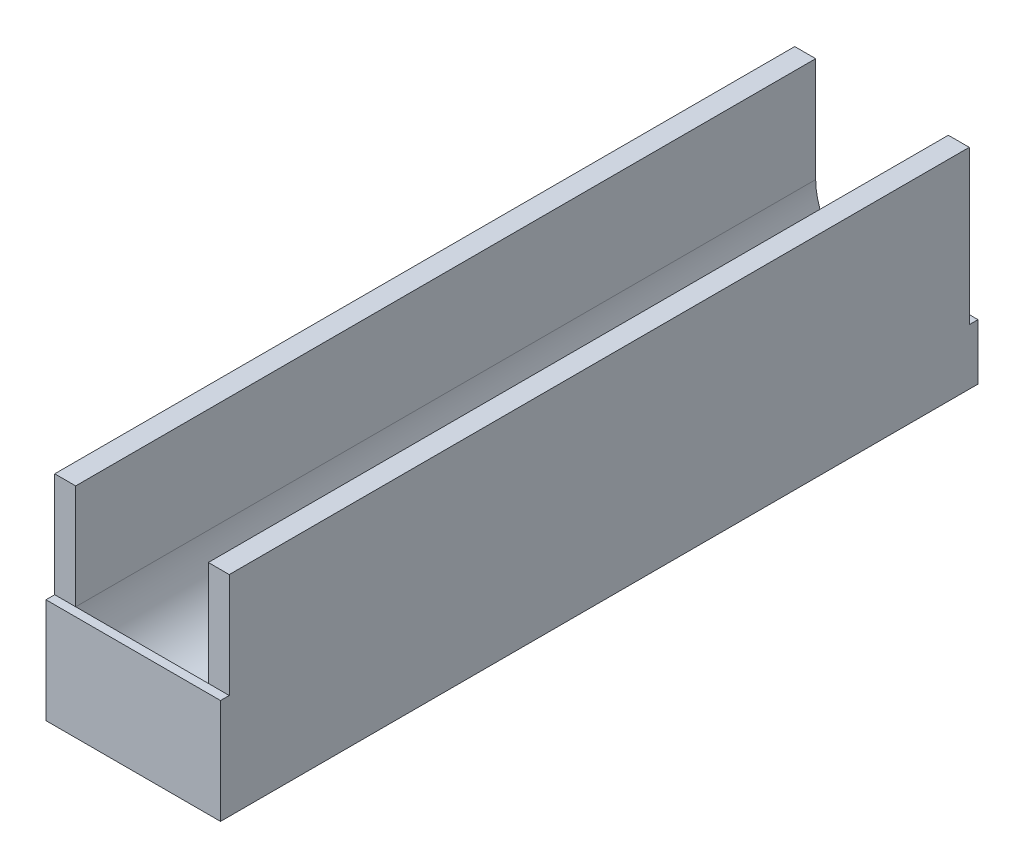
SolidWorks part; units mm, degrees
ref_plane "Front Plane" through (0, 0, 0) normal (0, 0, 1) x (1, 0, 0)
ref_plane "Top Plane" through (0, 0, 0) normal (0, 1, 0) x (1, 0, 0)
ref_plane "Right Plane" through (0, 0, 0) normal (1, 0, 0) x (0, 0, -1)
sketch "Sketch1" plane through (0, 0, 0) normal (0, 0, 1) x (1, 0, 0)
  line L1 (-15.875, 0) -> (15.875, 0)
  line L2 (-15.875, 0) -> (-15.875, 38.1)
  line L3 (-15.875, 38.1) -> (15.875, 38.1)
  line L4 (15.875, 0) -> (15.875, 38.1)
  dimension "D1" = 38.1
  dimension "D2" = 31.75
  dimension "D3" = 15.875
extrude "Boss-Extrude1" add sketch "Sketch1" along normal blind 134.62
sketch "Sketch2" plane through (0, 0, 134.62) normal (0, 0, 1) x (1, 0, 0)
  line L0 (-12.065, 19.05) -> (-12.065, 38.1)
  line L1 (15.875, 38.1) -> (-15.875, 38.1) construction
  line L2 (12.065, 19.05) -> (12.065, 38.1)
  line L3 (12.065, 38.1) -> (-12.065, 38.1)
  arc A2 (-12.065, 19.05) -> (12.065, 19.05) centre (0, 19.05) ccw
  dimension "D1" = 24.13
  dimension "D3" = 19.05
  dimension "D2" = 0
  dimension "D4" = 19.05
extrude "Cut-Extrude1" cut sketch "Sketch2" against normal through all
sketch "Sketch3" plane through (0, 0, 0) normal (0, -1, 0) x (1, 0, 0)
  line L0 (-15.875, 134.62) -> (15.875, 134.62) construction
  line L1 (-15.875, 0) -> (15.875, 0) construction
  circle A0 centre (-12.7, 128.27) radius 2
  circle A1 centre (12.7, 6.35) radius 2
  point P6 (0, 134.62)
  dimension "D1" = 4
  dimension "D2" = 4
  dimension "D6" = 6.35
  dimension "D3" = 12.7
  dimension "D4" = 12.7
  dimension "D5" = 6.35
extrude "Cut-Extrude2" cut sketch "Sketch3" against normal blind 7
sketch "Sketch4" plane through (0, 0, 134.62) normal (0, 0, 1) x (1, 0, 0)
  line L0 (-15.875, 38.1) -> (-15.875, 0) construction
  line L1 (15.875, 0) -> (-15.875, 0)
  line L2 (15.875, 0) -> (15.875, 19.05)
  line L3 (15.875, 19.05) -> (-15.875, 19.05)
  line L4 (-15.875, 0) -> (-15.875, 19.05)
  dimension "D1" = 19.05
extrude "Boss-Extrude2" add sketch "Sketch4" along normal blind 1.5875
sketch "Sketch5" plane through (0, 0, 0) normal (0, 0, -1) x (-1, 0, 0)
  line L0 (15.875, 38.1) -> (15.875, 0) construction
  line L1 (-15.875, 0) -> (15.875, 0)
  line L2 (-15.875, 0) -> (-15.875, 10.16)
  line L3 (-15.875, 10.16) -> (15.875, 10.16)
  line L4 (15.875, 0) -> (15.875, 10.16)
  dimension "D1" = 10.16
extrude "Boss-Extrude3" add sketch "Sketch5" along normal blind 1.5875
